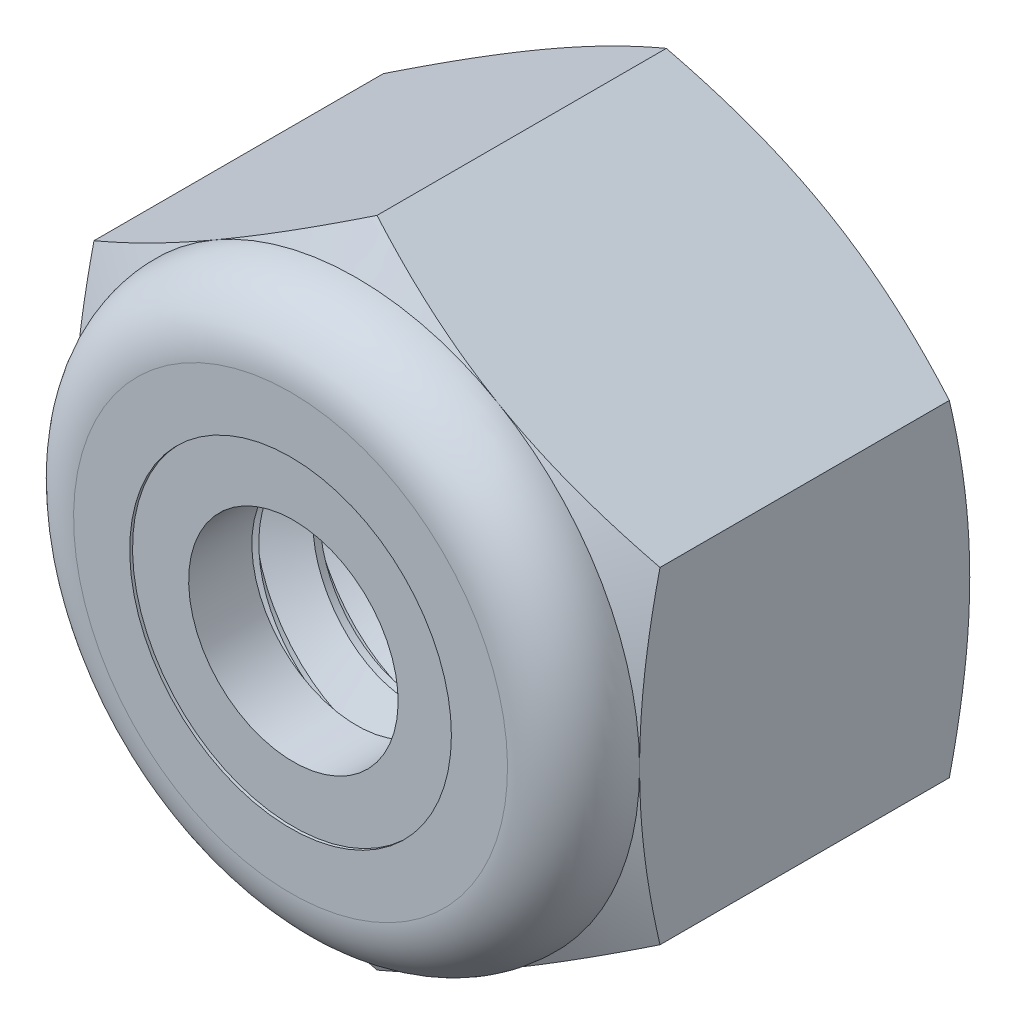
SolidWorks part; units mm, degrees
ref_plane "Front Plane" through (0, 0, 0) normal (0, 0, 1) x (1, 0, 0)
ref_plane "Top Plane" through (0, 0, 0) normal (0, 1, 0) x (1, 0, 0)
ref_plane "Right Plane" through (0, 0, 0) normal (1, 0, 0) x (0, 0, -1)
sketch "Sketch1" plane through (0, 0, 0) normal (0, 0, 1) x (1, 0, 0)
  line L1 (0, 2.3094) -> (-2, 1.1547)
  line L2 (-2, 1.1547) -> (-2, -1.1547)
  line L3 (-2, -1.1547) -> (0, -2.3094)
  line L4 (0, -2.3094) -> (2, -1.1547)
  line L5 (2, -1.1547) -> (2, 1.1547)
  line L6 (2, 1.1547) -> (0, 2.3094)
  circle A0 centre (0, 0) radius 2 construction
  circle A1 centre (0, 0) radius 1
  point P10 (0, -1)
  point P11 (0, 1)
  point P12 (0, 2)
  dimension "Thread Size" = 2
  dimension "Width" = 4
sketch "Sketch2" plane through (0, 0, 0) normal (1, 0, 0) x (0, 0, -1)
  line L0 (1.4, 0) -> (-1.4, 0) construction
  line L1 (-1.4, 1) -> (1.4, 1) construction
  line L2 (-1.38, -1.1368) -> (-2.67, -1.1368) construction
  line L3 (-1.775, 1.0433) -> (-1.375, 1.0433) construction
  line L4 (-1.375, 1.0433) -> (-1.575, 0.6969) construction
  line L5 (-1.575, 0.6969) -> (-1.775, 1.0433) construction
  line L6 (-1.75, 1) -> (-1.4, 1) construction
  line L7 (-1.6, 0.7402) -> (-1.55, 0.7402) construction
  line L8 (-1.575, 0.7402) -> (-1.575, 0.6969) construction
  line L9 (-1.575, 1) -> (-1.575, 1.0433) construction
  line L10 (-1.3875, 1.0217) -> (-1.7625, 1.0217)
  line L11 (-1.7625, 1.0217) -> (-1.6, 0.7402)
  line L12 (-1.6, 0.7402) -> (-1.55, 0.7402)
  line L13 (-1.55, 0.7402) -> (-1.3875, 1.0217)
  line L14 (1.4, 0) -> (2.67, 0)
  line L15 (2.67, 0) -> (2.67, 3.5794)
  line L16 (0, 3.5794) -> (0, 2.3094) construction
  line L17 (0, 2.3094) -> (0, 1.1547) construction
  line L18 (1.4, 2) -> (-0.9333, 2) construction
  line L19 (-1.6, -0.7402) -> (-1.55, -0.7402) construction
  line L20 (1.4, 2) -> (1.4, 0)
  line L21 (1.2557, 2.3094) -> (-0.7891, 2.3094)
  line L22 (1.4, 2) -> (1.2557, 2.3094)
  line L23 (-1.4, 0) -> (-1.4, 1.5333) construction
  line L24 (-0.9333, 2) -> (-0.7891, 2.3094)
  line L25 (2.67, 3.5794) -> (-2.67, 3.5794)
  line L26 (-1.4, 1.5333) -> (-2.67, 1.5333)
  line L27 (-2.67, 1.5333) -> (-2.67, 3.5794)
  line L28 (-1.38, 1.5333) -> (-1.38, 0.7402) construction
  line L29 (-1.38, 1.1368) -> (-2.67, 1.1368)
  line L30 (-2.67, 1.1368) -> (-2.67, 0)
  line L31 (-2.67, 0) -> (-0.9333, 0)
  line L32 (-0.9333, 0) -> (-0.9333, 1.98)
  line L33 (-1.38, 1.1368) -> (-1.38, 1.5333)
  arc A0 (-0.9333, 2) -> (-1.4, 1.5333) centre (-0.9333, 1.5333) ccw
  arc A1 (-0.9333, 1.98) -> (-1.38, 1.5333) centre (-0.9333, 1.5333) ccw
  point P4 (0, 0)
  point P18 (-1.575, 1.0217)
  point P22 (-1.575, 1.0217)
  point P33 (0, 2.3094)
  point P48 (-2.67, -1.1368)
  point P51 (-1.6, -0.7402)
  dimension "Height" = 2.8
  dimension "Pitch" = 0.4
  dimension "D1" = 0.05
  dimension "D2" = 1.27
  dimension "D3" = 25
  dimension "D4" = 0.4667
  dimension "D5" = 25
  dimension "D6" = 0.02
sketch "Sketch3" plane through (0, 0, 0) normal (0, 0, 1) x (1, 0, 0)
  line L0 (0, -2.3094) -> (2, -1.1547) construction
  line L1 (2, -1.1547) -> (2, 1.1547) construction
  line L2 (2, 1.1547) -> (0, 2.3094) construction
  line L3 (0, 2.3094) -> (-2, 1.1547) construction
  line L4 (-2, 1.1547) -> (-2, -1.1547) construction
  line L5 (-2, -1.1547) -> (0, -2.3094) construction
  line L6 (0, -2.3094) -> (2, -1.1547)
  line L7 (2, -1.1547) -> (2, 1.1547)
  line L8 (2, 1.1547) -> (0, 2.3094)
  line L9 (0, 2.3094) -> (-2, 1.1547)
  line L10 (-2, 1.1547) -> (-2, -1.1547)
  line L11 (-2, -1.1547) -> (0, -2.3094)
  circle A0 centre (0, 0) radius 1 construction
  circle A1 centre (0, 0) radius 1
extrude "Boss-Extrude1" add sketch "Sketch3" along normal mid plane 2.8
sketch "Sketch4" plane through (0, 0, 0) normal (1, 0, 0) x (0, 0, -1)
  line L0 (2.67, 3.5794) -> (-2.67, 3.5794) construction
  line L1 (-2.67, 1.5333) -> (-2.67, 3.5794) construction
  line L2 (-1.4, 1.5333) -> (-2.67, 1.5333) construction
  line L3 (-0.9333, 2) -> (-0.7891, 2.3094) construction
  line L4 (1.2557, 2.3094) -> (-0.7891, 2.3094) construction
  line L5 (1.4, 2) -> (1.2557, 2.3094) construction
  line L6 (1.4, 2) -> (1.4, 0) construction
  line L7 (1.4, 0) -> (2.67, 0) construction
  line L8 (2.67, 0) -> (2.67, 3.5794) construction
  line L9 (-2.67, 1.1368) -> (-2.67, 0) construction
  line L10 (-2.67, 0) -> (-0.9333, 0) construction
  line L11 (-0.9333, 0) -> (-0.9333, 1.98) construction
  line L12 (-1.38, 1.1368) -> (-1.38, 1.5333) construction
  line L13 (-1.38, 1.1368) -> (-2.67, 1.1368) construction
  line L14 (2.67, 3.5794) -> (-2.67, 3.5794)
  line L15 (-2.67, 1.5333) -> (-2.67, 3.5794)
  line L16 (-1.4, 1.5333) -> (-2.67, 1.5333)
  line L17 (-0.9333, 2) -> (-0.7891, 2.3094)
  line L18 (1.2557, 2.3094) -> (-0.7891, 2.3094)
  line L19 (1.4, 2) -> (1.2557, 2.3094)
  line L20 (1.4, 2) -> (1.4, 0)
  line L21 (1.4, 0) -> (2.67, 0)
  line L22 (2.67, 0) -> (2.67, 3.5794)
  line L23 (-2.67, 1.1368) -> (-2.67, 0)
  line L24 (-2.67, 0) -> (-0.9333, 0)
  line L25 (-0.9333, 0) -> (-0.9333, 1.98)
  line L26 (-1.38, 1.1368) -> (-1.38, 1.5333)
  line L27 (-1.38, 1.1368) -> (-2.67, 1.1368)
  arc A0 (-0.9333, 2) -> (-1.4, 1.5333) centre (-0.9333, 1.5333) ccw construction
  arc A1 (-0.9333, 1.98) -> (-1.38, 1.5333) centre (-0.9333, 1.5333) ccw construction
  arc A2 (-0.9333, 2) -> (-1.4, 1.5333) centre (-0.9333, 1.5333) ccw
  arc A3 (-0.9333, 1.98) -> (-1.38, 1.5333) centre (-0.9333, 1.5333) ccw
revolve "Cut-Revolve1" cut sketch "Sketch4" angle 360 about L0
sketch "Sketch5" plane through (0, 0, 0) normal (1, 0, 0) x (0, 0, -1)
  line L0 (-1.38, 1.5333) -> (-1.38, 0.7402) construction
  line L1 (-0.9333, 0) -> (-0.9333, 1.98) construction
  line L2 (-1.38, 1.5333) -> (-1.38, 0.7402)
  line L3 (-0.9333, 0.7402) -> (-0.9333, 1.98)
  line L4 (-1.38, 0.7402) -> (-0.9333, 0.7402)
  arc A0 (-0.9333, 1.98) -> (-1.38, 1.5333) centre (-0.9333, 1.5333) ccw construction
  arc A1 (-0.9333, 1.98) -> (-1.38, 1.5333) centre (-0.9333, 1.5333) ccw
revolve "Revolve1" add sketch "Sketch5" angle 360 about L0
sketch "Sketch6" plane through (0, 0, 1.4) normal (0, 0, 1) x (1, 0, 0)
  circle A0 centre (0, 0) radius 1 construction
  circle A1 centre (0, 0) radius 1
curve "Helix/Spiral1" pitch 0.4 height 3.2 radius 1 centre (0, 0, 1.4) axis (0, 0, -1) start towards (0, 1, 0)
sketch "Sketch7" plane through (0, 0, 0) normal (1, 0, 0) x (0, 0, -1)
  line L0 (-1.7625, 1.0217) -> (-1.6, 0.7402) construction
  line L1 (-1.6, 0.7402) -> (-1.55, 0.7402) construction
  line L2 (-1.55, 0.7402) -> (-1.3875, 1.0217) construction
  line L3 (-1.3875, 1.0217) -> (-1.7625, 1.0217) construction
  line L4 (-1.7625, 1.0217) -> (-1.6, 0.7402)
  line L5 (-1.6, 0.7402) -> (-1.55, 0.7402)
  line L6 (-1.55, 0.7402) -> (-1.3875, 1.0217)
  line L7 (-1.3875, 1.0217) -> (-1.7625, 1.0217)
sweep "Sweep1" add profiles "Sketch7" path "Helix/Spiral1"
sketch "Sketch8" plane through (0, 0, -1.4) normal (0, 0, -1) x (-1, 0, 0)
  circle A2 centre (0, 0) radius 1.0217
  point P2 (0, 1.0217)
extrude "Cut-Extrude1" cut sketch "Sketch8" along normal through all and the other way through all draft 60
sketch "Sketch9" plane through (0, 0, 0.9333) normal (0, 0, 1) x (1, 0, 0)
  circle A2 centre (0, 0) radius 1.0217
  circle A3 centre (0, 0) radius 0.7402 construction
  point P2 (0, 1.0217)
  point P4 (0, 0.7402)
extrude "Cut-Extrude2" cut sketch "Sketch9" along normal through all and the other way through all draft 60
equation "\"D1@Sketch2\" = \"Pitch@Sketch2\" / 8"
equation "\"D4@Sketch2\"=\"Height@Sketch2\"/6"
equation "\"D1@Boss-Extrude1\"=\"Height@Sketch2\""
equation "\"D3@Helix/Spiral1\"=\"Height@Sketch2\"+\"Pitch@Sketch2\""
equation "\"D4@Helix/Spiral1\"=\"Pitch@Sketch2\""
equation "\"D6@Sketch2\"=\"Pitch@Sketch2\"*0.05"
